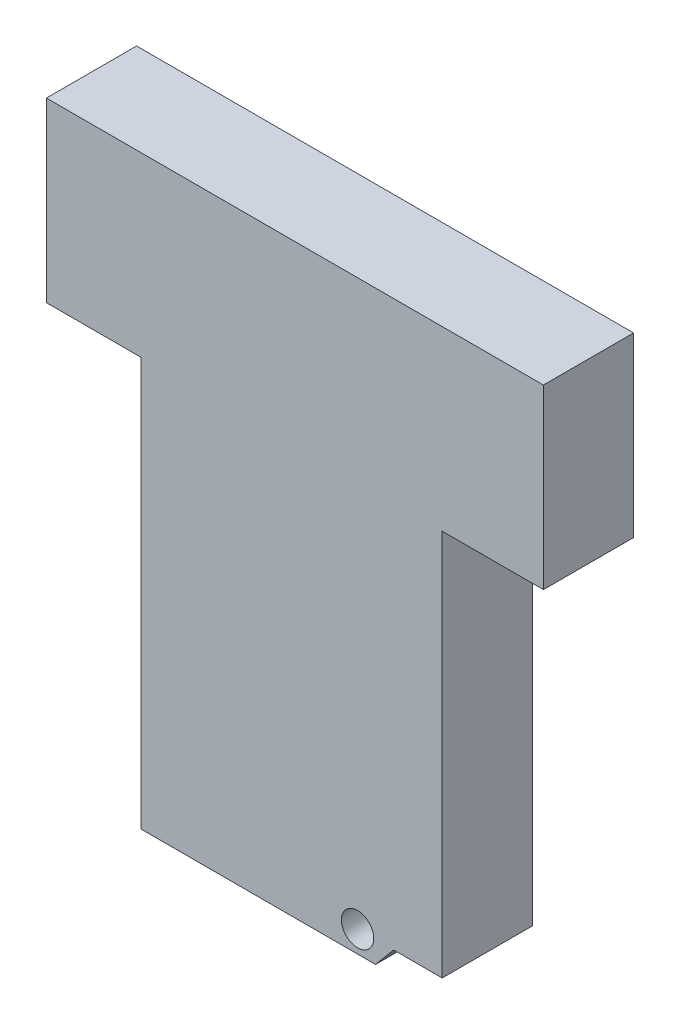
SolidWorks part; units mm, degrees
ref_plane "Front Plane" through (0, 0, 0) normal (0, 0, 1) x (1, 0, 0)
ref_plane "Top Plane" through (0, 0, 0) normal (0, 1, 0) x (1, 0, 0)
ref_plane "Right Plane" through (0, 0, 0) normal (1, 0, 0) x (0, 0, -1)
sketch "Sketch1" plane through (0, 0, 0) normal (0, 0, 1) x (1, 0, 0)
  line L0 (-70, 3.04) -> (-59.1939, 3.04)
  line L1 (-23.643, 0) -> (-56.643, 0)
  line L2 (0, 3.04) -> (0, 82.5)
  line L3 (0, 82.5) -> (-70, 82.5)
  line L4 (-70, 3.04) -> (-70, 82.5)
  line L5 (0, 3.04) -> (-21.0922, 3.04)
  line L6 (-56.643, 0) -> (-23.643, 0)
  line L7 (-59.1939, 3.04) -> (-56.643, 0)
  line L8 (-23.643, 0) -> (-21.0922, 3.04)
  line L13 (-70, 3.04) -> (-70, 57.54)
  line L14 (-70, 57.54) -> (-56.643, 57.54)
  line L15 (-70, 57.54) -> (-70, 3.04)
  line L16 (-70, 3.04) -> (-59.1939, 3.04)
  line L17 (-56.643, 57.54) -> (-56.643, 0)
  line L20 (0, 57.54) -> (-14.2608, 57.54)
  line L21 (0, 57.54) -> (0, 3.04)
  line L22 (0, 3.04) -> (-14.2608, 3.04)
  line L23 (-14.2608, 57.54) -> (-14.2608, 3.04)
  circle A0 centre (-26.1739, 3.04) radius 2.2776
  point P4 (0, 0)
  point P17 (0, 0)
  point P19 (-56.391, 0.2342)
  dimension "D8" = 4.5553
  dimension "D15" = 26.3498
  dimension "D1" = 3.04
  dimension "70mm" = 70
  dimension "33" = 33
  dimension "D2" = 140
  dimension "D3" = 140
  dimension "D4" = 79.46
  dimension "D5" = 3.04
  dimension "D6" = 18.1116
  dimension "D7" = 70
  dimension "33.02m" = 33.02
  dimension "D17" = 14.2608
  dimension "D18" = 24.96
  dimension "D19" = 24.96
extrude "Boss-Extrude1" add sketch "Sketch1" along normal blind 12.7 contours L0 L7 L1 L8 L5 L2 L3 L4
extrude "Cut-Extrude6" cut sketch "Sketch1<9>" along normal blind 12.7 contours L17 L14 L4 L0 L7 | L20 L23 L5 L2 | A0 region at (-63.2906, 30.1403, 0) region at (-7.1304, 30.29, 0)
sketch "Sketch1<9>" plane through (0, 0, 0) normal (0, 0, 1) x (1, 0, 0) same geometry as "Sketch1"
